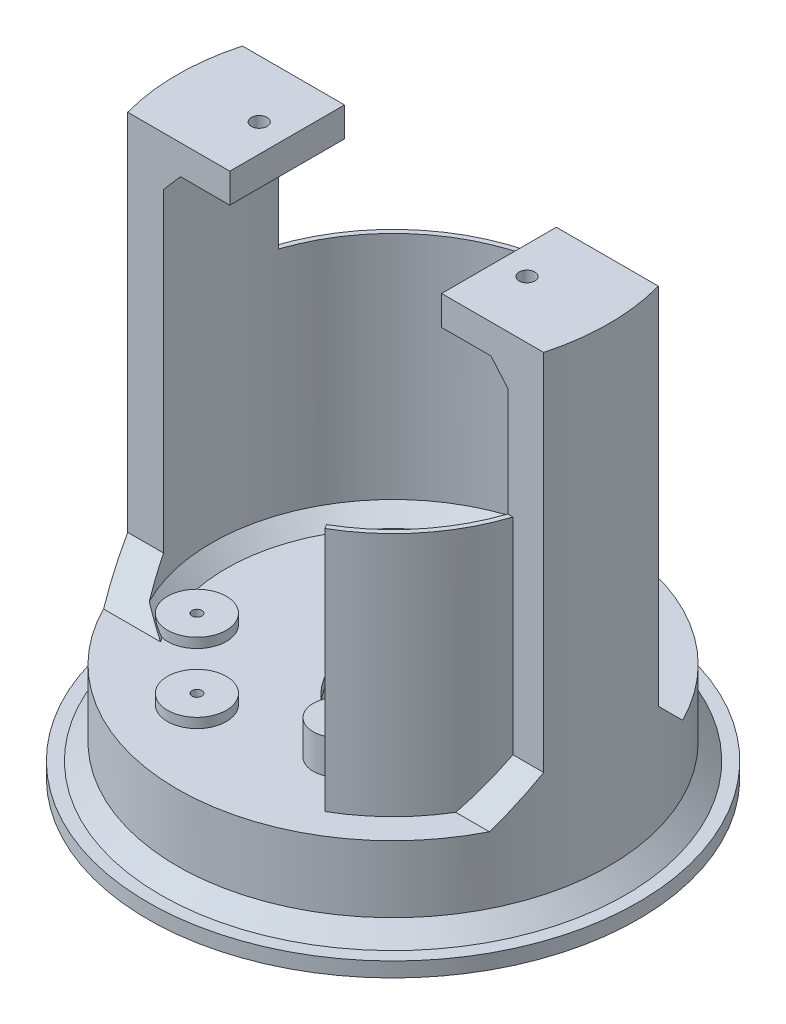
SolidWorks part; units mm, degrees
ref_plane "Front Plane" through (0, 0, 0) normal (0, 0, 1) x (1, 0, 0)
ref_plane "Top Plane" through (0, 0, 0) normal (0, 1, 0) x (1, 0, 0)
ref_plane "Right Plane" through (0, 0, 0) normal (1, 0, 0) x (0, 0, -1)
sketch "Sketch2" plane through (0, 0, 0) normal (0, 1, 0) x (1, 0, 0)
  line L0 (-11.2, 0) -> (11.2, 0) construction
  line L1 (-16.1, 5.85) -> (16.1, 5.85)
  line L2 (-16.1, 5.85) -> (-16.1, -5.85)
  line L3 (-16.1, -5.85) -> (16.1, -5.85)
  line L4 (16.1, 5.85) -> (16.1, -5.85)
  line L5 (-11.2, 5.85) -> (-11.2, -5.85)
  line L6 (11.2, 5.85) -> (11.2, -5.85)
  line L7 (-11.2, 0) -> (11.2, 0) construction
  line L8 (16.1, 0) -> (16.85, 0) construction
  line L9 (0, 5.85) -> (0, -5.85) construction
  line L10 (-11.2, 19.5903) -> (-11.2, -21.4075) construction
  line L11 (11.2, 20.2691) -> (11.2, -20.7287) construction
  line L12 (-16.1, 5.85) -> (-11.2, 5.85) construction
  line L13 (11.2, 5.85) -> (16.1, 5.85)
  circle A0 centre (5.35, 0) radius 11.5
  circle A3 centre (5.35, 0) radius 5.85
  circle A6 centre (0, 0) radius 17.1299 construction
  circle A7 centre (0, 0) radius 21 construction
  circle A8 centre (-13.65, 0) radius 1
  circle A9 centre (13.65, 0) radius 1
  dimension "D1" = 23
  dimension "D7" = 2.45
  dimension "D8" = 42
  dimension "D9" = 3.8701
  dimension "D6" = 2
  dimension "D2" = 32.2
  dimension "D3" = 11.7
  dimension "D4" = 22.4
  dimension "D5" = 4.9
  dimension "4.9" = 4.9
sketch "Sketch1" plane through (0, 0, 0) normal (0, 1, 0) x (1, 0, 0)
  circle A2 centre (0, 0) radius 22
  dimension "44" = 44
extrude "Boss-Extrude1" add sketch "Sketch1" along normal blind 10
sketch "Sketch3" plane through (0, 10, 0) normal (0, 1, 0) x (1, 0, 0)
  line L9 (-17.5507, 5.85) -> (-21.208, 5.85)
  line L11 (-17.5507, -5.85) -> (-21.208, -5.85)
  line L12 (0, 7.3847) -> (0, -7.8515) construction
  line L13 (17.5507, -5.85) -> (21.208, -5.85)
  line L14 (17.5507, 5.85) -> (21.208, 5.85)
  circle A10 centre (0, 0) radius 22 construction
  arc A11 (-21.208, 5.85) -> (-21.208, -5.85) centre (0, 0) ccw
  arc A12 (-17.5507, 5.85) -> (-17.5507, -5.85) centre (0, 0) ccw
  arc A13 (17.5507, 5.85) -> (17.5507, -5.85) centre (0, 0) cw
  arc A14 (21.208, 5.85) -> (21.208, -5.85) centre (0, 0) cw
  dimension "D1" = 3.5
extrude "Boss-Extrude2" add sketch "Sketch3" along normal blind 38.1
sketch "Sketch8" plane through (0, 0, 0) normal (0, -1, 0) x (1, 0, 0)
  circle A0 centre (0, 0) radius 21
  circle A1 centre (0, 0) radius 22 construction
  dimension "D1" = 1
extrude "Cut-Extrude2" cut sketch "Sketch8" against normal blind 9
chamfer "Chamfer1" distance 1 angle 30 1 edges at (0, 9, -21) first distance on face at (0, 9, -21)
sketch "Sketch9" plane through (0, 10, 0) normal (0, 1, 0) x (1, 0, 0)
  circle A0 centre (5.35, 0) radius 10
  dimension "D1" = 20
extrude "Boss-Extrude5" add sketch "Sketch9" against normal blind 3
sketch "Sketch10" plane through (0, 10, 0) normal (0, 1, 0) x (1, 0, 0)
  circle A0 centre (5.35, 0) radius 10 construction
  circle A1 centre (5.35, 0) radius 9
  circle A2 centre (5.35, 0) radius 5
  dimension "D1" = 20
  dimension "D2" = 18
  dimension "D3" = 10
extrude "Cut-Extrude3" cut sketch "Sketch10" against normal blind 1.5
sketch "Sketch11" plane through (0, 10, 0) normal (0, 1, 0) x (1, 0, 0)
  circle A0 centre (5.35, 0) radius 4
  dimension "D1" = 8
extrude "Cut-Extrude4" cut sketch "Sketch11" against normal through all
sketch "Sketch12" plane through (0, 10, 0) normal (0, 1, 0) x (1, 0, 0)
  circle A0 centre (5.35, 0) radius 4 construction
  circle A1 centre (5.35, 0) radius 5
  circle A2 centre (5.35, 0) radius 5
  circle A3 centre (5.35, 0) radius 4
  dimension "D1" = 0
extrude "Boss-Extrude6" add sketch "Sketch12" along normal blind 4
sketch "Sketch13" plane through (0, 10, 0) normal (0, 1, 0) x (1, 0, 0)
  line L0 (5.35, 11) -> (5.35, -11) construction
  circle A0 centre (5.35, 0) radius 11 construction
  circle A1 centre (5.35, 11) radius 2.5
  circle A2 centre (5.35, -11) radius 2.5
  dimension "D1" = 22
  dimension "D2" = 5
extrude "Boss-Extrude7" add sketch "Sketch13" along normal blind 3.5 and the other way blind 5
sketch "Sketch14" plane through (0, 13.5, 0) normal (0, 1, 0) x (1, 0, 0)
  circle A0 centre (5.35, -11) radius 0.9
  circle A1 centre (5.35, 11) radius 0.9
  dimension "D1" = 1.8
extrude "Cut-Extrude5" cut sketch "Sketch14" against normal blind 7
chamfer "Chamfer2" distance 0.3 angle 45 1 edges at (5.35, 14, 5)
sketch "Sketch17" plane through (0, 10, 0) normal (0, 1, 0) x (1, 0, 0)
  line L0 (0, 0) -> (-6.4645, -13.5355) construction
  line L1 (0, 0) -> (-13.5355, -6.4645) construction
  line L2 (-13.5355, -6.4645) -> (-6.4645, -13.5355) construction
  line L3 (0, 0) -> (-10, -10) construction
  line L4 (0, 0) -> (-8.5212, 0) construction
  circle A0 centre (0, 0) radius 15 construction
  circle A1 centre (-13.5355, -6.4645) radius 3
  circle A2 centre (-6.4645, -13.5355) radius 3
  dimension "D1" = 30
  dimension "D4" = 6
  dimension "D2" = 10
  dimension "D3" = 45
extrude "Boss-Extrude9" add sketch "Sketch17" against normal blind 2 and the other way blind 1
sketch "Sketch18" plane through (0, 11, 0) normal (0, 1, 0) x (1, 0, 0)
  circle A0 centre (-6.4645, -13.5355) radius 0.5
  circle A1 centre (-13.5355, -6.4645) radius 0.5
  dimension "D1" = 1
extrude "Cut-Extrude6" cut sketch "Sketch18" against normal through all
sketch "Sketch19" plane through (0, 0, 0) normal (0, -1, 0) x (1, 0, 0)
  circle A0 centre (0, 0) radius 25
  circle A1 centre (0, 0) radius 21 construction
  circle A2 centre (0, 0) radius 21
  dimension "D1" = 4
extrude "Boss-Extrude10" add sketch "Sketch19" against normal blind 1.5
chamfer "Chamfer3" distance 0.5 angle 45 4 edges at (5.35, 8.5, 8.5) (14.35, 8.5, 0) (-3.65, 8.5, 0) (5.35, 8.5, -8.5)
sketch "Sketch24" plane through (0, 48.1, 0) normal (0, 1, 0) x (1, 0, 0)
  line L0 (0, 8.598) -> (0, -8.7349) construction
  line L1 (-17.5507, 5.85) -> (-11.7, 5.85)
  line L2 (-17.5507, 5.85) -> (-21.208, 5.85)
  line L3 (-21.208, -5.85) -> (-17.5507, -5.85)
  line L4 (-17.5507, 5.85) -> (-21.208, 5.85)
  line L5 (-21.208, -5.85) -> (-17.5507, -5.85)
  line L6 (-16.1, 5.85) -> (16.1, 5.85) construction
  line L7 (-11.7, 5.85) -> (-11.7, -5.85)
  line L8 (-16.1, -5.85) -> (16.1, -5.85) construction
  line L9 (-11.7, -5.85) -> (-17.5507, -5.85)
  line L10 (-11.2, 5.85) -> (-11.2, -5.85) construction
  line L11 (11.7, -5.85) -> (17.5507, -5.85)
  line L12 (11.7, 5.85) -> (11.7, -5.85)
  line L13 (21.208, -5.85) -> (17.5507, -5.85)
  line L14 (17.5507, 5.85) -> (21.208, 5.85)
  line L15 (17.5507, 5.85) -> (11.7, 5.85)
  arc A0 (21.208, 5.85) -> (21.208, -5.85) centre (0, 0) cw
  circle A1 centre (-13.65, 0) radius 0.8
  arc A2 (-17.5507, 5.85) -> (-17.5507, -5.85) centre (0, 0) ccw
  arc A3 (-21.208, 5.85) -> (-21.208, -5.85) centre (0, 0) ccw
  arc A5 (-21.208, 5.85) -> (-21.208, -5.85) centre (0, 0) ccw
  circle A6 centre (13.65, 0) radius 0.8
  dimension "D3" = 1.6
  dimension "D2" = 0.5
  dimension "D1" = 0
extrude "Boss-Extrude12" add sketch "Sketch24" along normal blind 3
sketch "Sketch26" plane through (0, 10, 0) normal (0, 1, 0) x (1, 0, 0)
  circle A0 centre (0, 0) radius 21.5
  circle A2 centre (0, 0) radius 22
  dimension "D1" = 0.5
extrude "Boss-Extrude13" [suppressed] add sketch "Sketch26" along normal up to surface (41.1 mm away)
sketch "Sketch27" plane through (0, 10, 0) normal (0, 1, 0) x (1, 0, 0)
  line L0 (0, 0) -> (-13.435, -13.435) construction
  line L1 (0, 0) -> (-7.3467, 0) construction
  line L2 (0, 0) -> (-21.208, -5.85) construction
  line L3 (0, 0) -> (9.5, -16.4545) construction
  line L4 (-18.316, -5.0523) -> (-17.834, -4.9193)
  line L5 (9.25, -16.0215) -> (9.5, -16.4545)
  arc A0 (9.5, -16.4545) -> (-18.316, -5.0523) centre (0, 0) ccw
  arc A1 (9.25, -16.0215) -> (-17.834, -4.9193) centre (0, 0) ccw
  arc A2 (-17.5507, 5.85) -> (-17.5507, -5.85) centre (0, 0) ccw construction
  dimension "D3" = 0.5
  dimension "D1" = 45
  dimension "D2" = 120
extrude "Boss-Extrude14" add sketch "Sketch27" along normal blind 25
fillet "Fillet1" radius 4 4 edges at (19.6425, 10, -5.85) (19.6425, 10, 5.85) (-19.6425, 10, -5.85) (-19.3793, 10, 5.85) profile chamfer
sketch "Sketch28" plane through (-11.7, 0, 0) normal (1, 0, 0) x (0, 0, -1)
  line L4 (-5.85, 48.1) -> (5.85, 48.1)
  line L5 (5.85, 48.1) -> (5.85, 51.1)
  line L6 (5.85, 51.1) -> (-5.85, 51.1)
  line L7 (-5.85, 51.1) -> (-5.85, 48.1)
  line L8 (-5.85, 48.1) -> (5.85, 48.1)
  line L9 (5.85, 48.1) -> (5.85, 51.1)
  line L10 (5.85, 51.1) -> (-5.85, 51.1)
  line L11 (-5.85, 51.1) -> (-5.85, 48.1)
  dimension "D1" = 0
extrude "Boss-Extrude15" add sketch "Sketch28" along normal blind 0.9
sketch "Sketch29" plane through (11.7, 0, 0) normal (-1, 0, 0) x (0, 0, 1)
  line L4 (-5.85, 48.1) -> (5.85, 48.1)
  line L5 (5.85, 48.1) -> (5.85, 51.1)
  line L6 (5.85, 51.1) -> (-5.85, 51.1)
  line L7 (-5.85, 51.1) -> (-5.85, 48.1)
  line L8 (-5.85, 48.1) -> (5.85, 48.1)
  line L9 (5.85, 48.1) -> (5.85, 51.1)
  line L10 (5.85, 51.1) -> (-5.85, 51.1)
  line L11 (-5.85, 51.1) -> (-5.85, 48.1)
  dimension "D1" = 0
extrude "Boss-Extrude16" add sketch "Sketch29" along normal blind 0.9
chamfer "Chamfer4" distance 2 angle 39 2 edges at (18.5, 48.1, 0) (-18.5, 48.1, 0) first distance on face at (1.0279, 33.3039, -0.0756)
chamfer "Chamfer5" distance 1.5 angle 45 1 edges at (4.4489, 10, -17.9571)
chamfer "Chamfer7" distance 1.7 angle 45 1 edges at (0, 1.5, -22)
